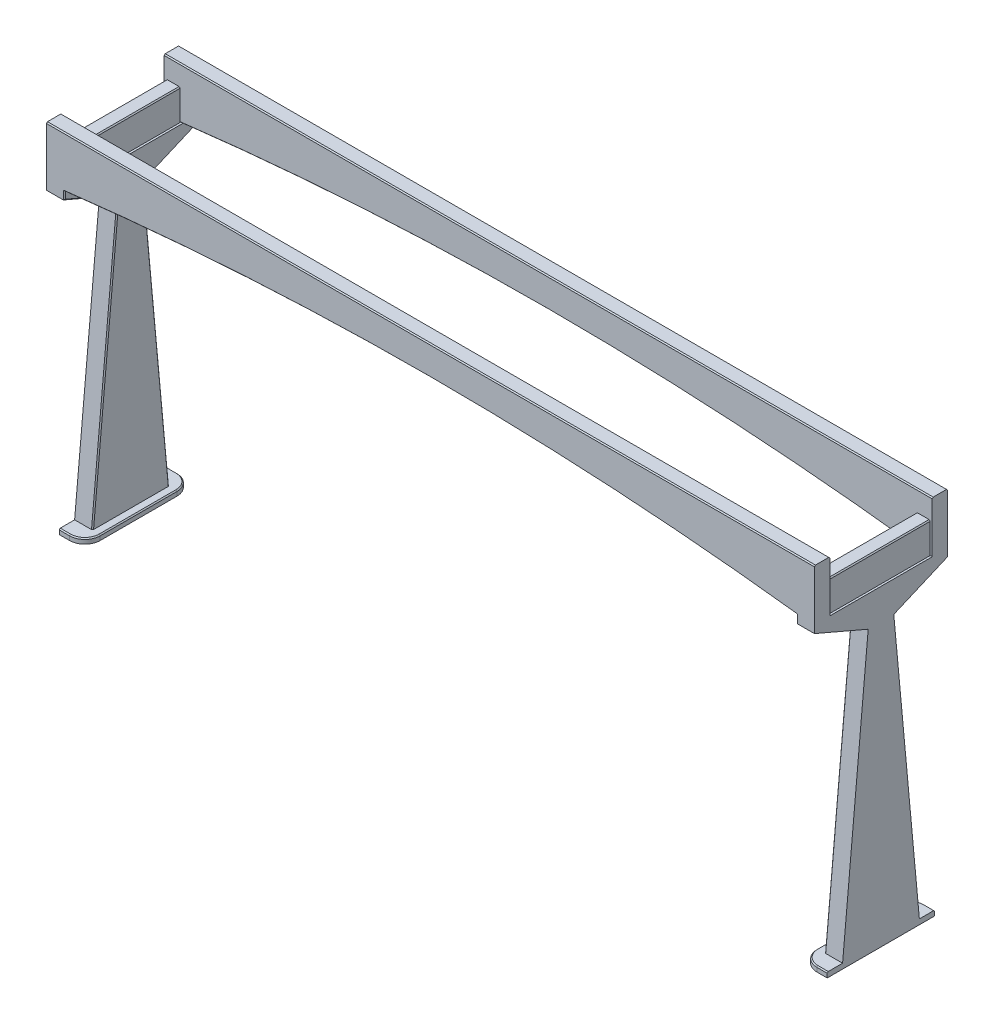
SolidWorks part; units mm, degrees
ref_plane "Front Plane" through (0, 0, 0) normal (0, 0, 1) x (1, 0, 0)
ref_plane "Top Plane" through (0, 0, 0) normal (0, 1, 0) x (1, 0, 0)
ref_plane "Right Plane" through (0, 0, 0) normal (1, 0, 0) x (0, 0, -1)
sketch "Sketch1" plane through (0, 0, 0) normal (0, 0, 1) x (1, 0, 0)
  line L0 (0, 0) -> (1500, 0)
  line L1 (0, 0) -> (0, -100)
  line L2 (0, -100) -> (35, -100)
  line L3 (1500, 0) -> (1500, -100)
  line L4 (1500, -100) -> (1465, -100)
  arc A0 (35, -100) -> (1465, -100) centre (750, -6057.2456) cw
  dimension "D4" = 6000
  dimension "D1" = 1500
  dimension "D2" = 100
  dimension "D3" = 35
extrude "Boss-Extrude1" add sketch "Sketch1" along normal blind 30
sketch "Sketch2" plane through (0, 0, 0) normal (0, 0, -1) x (-1, 0, 0)
  line L0 (-1482.5, -100) -> (-1482.5, -40) construction
  line L1 (-1465, -100) -> (-1500, -100) construction
  line L2 (-17.5, -100) -> (-17.5, -40) construction
  line L3 (0, -100) -> (-35, -100) construction
  line L4 (-750, 0) -> (-750, -150) construction
  line L5 (-1495.9635, -100) -> (-1469.0365, -100)
  line L6 (-1495.9635, -100) -> (-1495.9635, -40)
  line L7 (-1495.9635, -40) -> (-1469.0365, -40)
  line L8 (-1469.0365, -100) -> (-1469.0365, -40)
  line L9 (-1495.9635, -100) -> (-1469.0365, -40) construction
  line L10 (-1495.9635, -40) -> (-1469.0365, -100) construction
  line L11 (-1500, 0) -> (0, 0) construction
  line L12 (-4.0365, -40) -> (-30.9635, -40)
  line L13 (-30.9635, -100) -> (-30.9635, -40)
  line L14 (-4.0365, -100) -> (-30.9635, -100)
  line L15 (-4.0365, -100) -> (-4.0365, -40)
  point P8 (-1482.5, -70)
  dimension "D1" = 60
  dimension "D2" = 26.927
  dimension "D3" = 150
extrude "Boss-Extrude2" add sketch "Sketch2" along normal blind 200
sketch "Sketch3" plane through (0, 0, -200) normal (0, 0, -1) x (-1, 0, 0)
  line L5 (0, -100) -> (0, 0)
  line L6 (-35, -100) -> (0, -100)
  line L7 (-1500, -100) -> (-1465, -100)
  line L8 (-1500, 0) -> (-1500, -100)
  line L9 (0, 0) -> (-1500, 0)
  line L10 (0, -100) -> (0, 0)
  line L11 (-35, -100) -> (0, -100)
  line L12 (-1500, -100) -> (-1465, -100)
  line L13 (-1500, 0) -> (-1500, -100)
  line L14 (0, 0) -> (-1500, 0)
  arc A1 (-35, -100) -> (-1465, -100) centre (-750, -6057.2456) ccw
  arc A2 (-35, -100) -> (-1465, -100) centre (-750, -6057.2456) ccw
  dimension "D1" = 0
extrude "Boss-Extrude3" add sketch "Sketch3" along normal blind 30
sketch "Sketch5" plane through (4.0365, 0, 0) normal (-1, 0, 0) x (0, 0, 1)
  line L0 (-200, -100) -> (0, -100) construction
  line L1 (-200, -100) -> (0, -100)
  line L2 (-200, -100) -> (-230, -100)
  line L3 (-230, -100) -> (-230, -115)
  line L4 (-230, -115) -> (-125, -160)
  line L5 (0, -100) -> (30, -100)
  line L6 (30, -100) -> (30, -115)
  line L7 (30, -115) -> (-75, -160)
  line L8 (-100, -100) -> (-100, -700) construction
  line L9 (-100, -700) -> (-25, -700)
  line L10 (-25, -700) -> (-75, -160)
  line L11 (-100, -700) -> (-175, -700)
  line L12 (-175, -700) -> (-125, -160)
  line L13 (-125, -160) -> (-75, -160) construction
  point P10 (-153.9047, -167.3165)
  point P13 (-301.1768, -100)
  point P14 (0, 0)
  point P15 (0, 0)
  point P16 (-156.3032, -163.9611)
  point P17 (0, 0)
  dimension "D1" = 600
  dimension "D2" = 75
  dimension "D3" = 75
  dimension "D4" = 60
  dimension "D5" = 15
  dimension "D6" = 50
extrude "Boss-Extrude4" add sketch "Sketch5" along normal up to surface (4.0365 mm away) and the other way up to vertex (30.9635 mm away) up to face at (0, -50, -215) other way up to point (35, -100, -200)
sketch "Sketch6" plane through (0, -700, 0) normal (0, -1, 0) x (1, 0, 0)
  line L0 (0, -25) -> (0, 5)
  line L1 (0, 5) -> (50, 5)
  line L2 (50, 5) -> (50, -205)
  line L3 (50, -205) -> (0, -205)
  line L4 (0, -205) -> (0, -175)
  line L5 (0, -175) -> (0, -25)
  dimension "D1" = 50
  dimension "D2" = 30
extrude "Boss-Extrude5" add sketch "Sketch6" along normal blind 10
fillet "Fillet1" radius 30 2 edges at (50, -705, -205) (50, -705, 5)
ref_plane "Plane1" through (750, 0, 0) normal (1, 0, 0) x (0, 0, -1)
sketch "Sketch7" plane through (750, 0, 0) normal (1, 0, 0) x (0, 0, -1)
  line L0 (230, 0) -> (230, -100) construction
  line L1 (-30, 0) -> (230, 0)
  line L2 (-30, 0) -> (-30, -710)
  line L3 (-30, -710) -> (230, -710)
  line L4 (230, 0) -> (230, -710)
  line L5 (175, -710) -> (25, -710) construction
extrude "Cut-Extrude1" cut sketch "Sketch7" along normal through all
mirror "Mirror2" about plane through (750, 0, 0) normal (1, 0, 0) of bodies 106
chamfer "Chamfer1" distance 2 angle 45 4 edges at (750, 0, -230) (750, 0, -200) (750, 0, 0) (750, 0, 30)
chamfer "Chamfer2" distance 2 angle 45 4 edges at (4.0365, -40, -100) (30.9635, -40, -100) (1469.0365, -40, -100) (1495.9635, -40, -100)
chamfer "Chamfer3" distance 2 angle 45 12 edges at (1465, -107.5, 30) (1465, -137.5, -22.5) (1465, -430, -50) (1465, -107.5, -230) (1465, -137.5, -177.5) (1465, -430, -150) (35, -107.5, -230) (35, -137.5, -177.5) (35, -430, -150) (35, -430, -50) (35, -137.5, -22.5) (35, -107.5, 30)
chamfer "Chamfer4" distance 2 angle 45 10 edges at (10, -700, 5) (41.2132, -700, -3.7868) (50, -700, -100) (41.2132, -700, -196.2132) (10, -700, -205) (1490, -700, 5) (1458.7868, -700, -3.7868) (1450, -700, -100) (1458.7868, -700, -196.2132) (1490, -700, -205)
chamfer "Chamfer6" distance 2 angle 45 4 edges at (750, -57.2456, 30) (750, -57.2456, 0) (750, -57.2456, -200) (750, -57.2456, -230)
sketch "Sketch9" plane through (0, 0, 0) normal (0, 1, 0) x (1, 0, 0)
  line L0 (0, 215) -> (1500, 215)
  line L1 (0, 228) -> (0, 202) construction
  line L2 (1500, 228) -> (1500, 202) construction
  line L3 (1500, -15) -> (0, -15)
  line L4 (1500, -28) -> (1500, -2) construction
  line L5 (0, -28) -> (0, -2) construction
